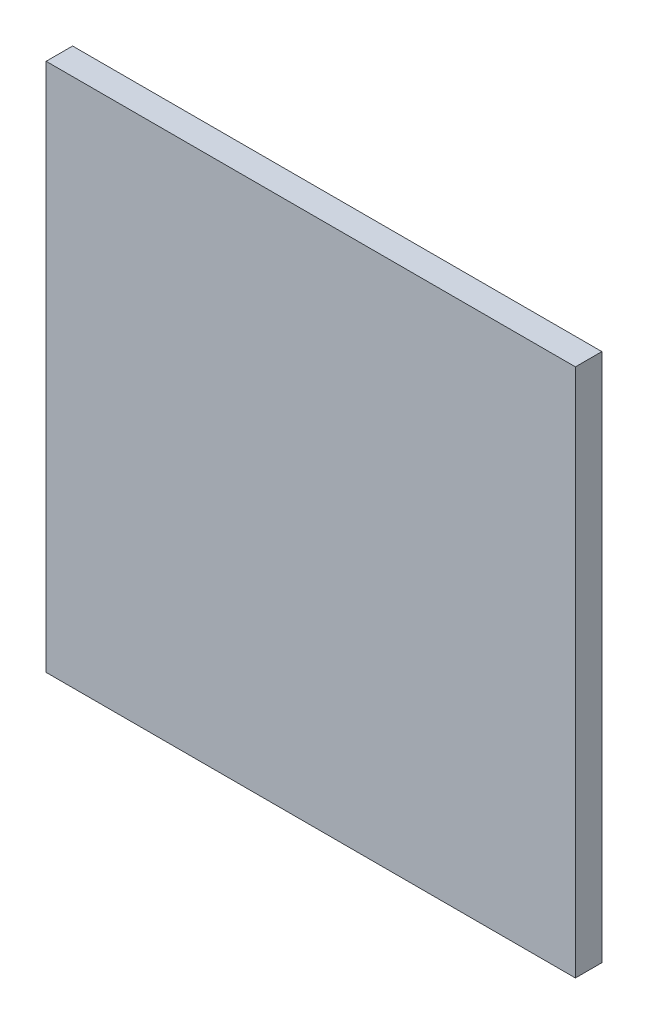
SolidWorks part; units mm, degrees
ref_plane "Front Plane" through (0, 0, 0) normal (0, 0, 1) x (1, 0, 0)
ref_plane "Top Plane" through (0, 0, 0) normal (0, 1, 0) x (1, 0, 0)
ref_plane "Right Plane" through (0, 0, 0) normal (1, 0, 0) x (0, 0, -1)
sketch "Sketch1" plane through (0, 0, 0) normal (0, 0, 1) x (1, 0, 0)
  line L1 (0, 0) -> (300, 0)
  line L2 (0, 0) -> (0, 300)
  line L3 (0, 300) -> (300, 300)
  line L4 (300, 0) -> (300, 300)
extrude "Boss-Extrude1" add sketch "Sketch1" along normal blind 15
